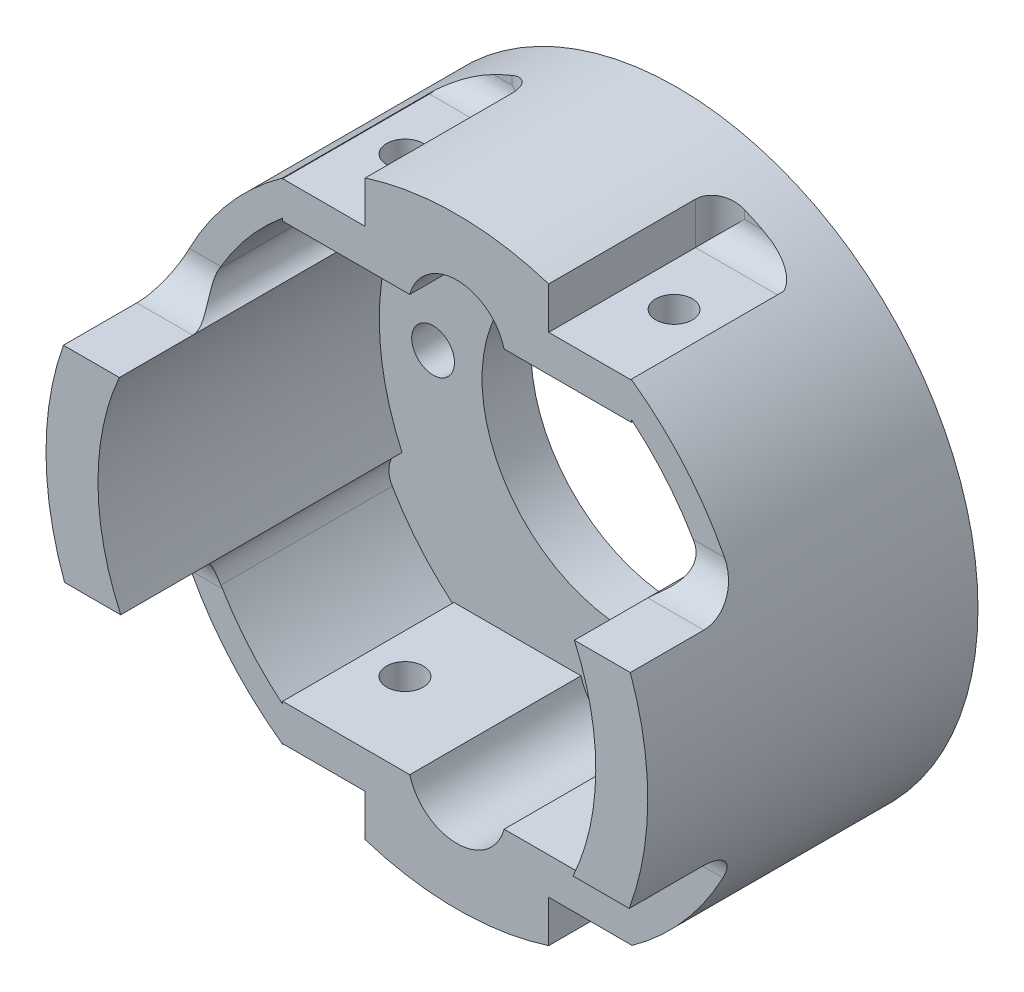
SolidWorks part; units mm, degrees
ref_plane "Front Plane" through (0, 0, 0) normal (0, 0, 1) x (1, 0, 0)
ref_plane "Top Plane" through (0, 0, 0) normal (0, 1, 0) x (1, 0, 0)
ref_plane "Right Plane" through (0, 0, 0) normal (1, 0, 0) x (0, 0, -1)
sketch "Sketch2" plane through (0, 0, 0) normal (0, 0, 1) x (1, 0, 0)
  circle A0 centre (0, 0) radius 11.95 construction
  circle A1 centre (0, 0) radius 24.6 construction
  circle A2 centre (0, 0) radius 11.95
  circle A3 centre (0, 0) radius 24.6
  circle A4 centre (-15.95, 0) radius 1.75
  circle A5 centre (0, 15.95) radius 1.75
  circle A6 centre (15.95, 0) radius 1.75
  circle A7 centre (0, -15.95) radius 1.75
  dimension "D1" = 3.5
extrude "Boss-Extrude1" add sketch "Sketch2" along normal blind 4
sketch "Sketch4" plane through (0, 0, 4) normal (0, 0, 1) x (1, 0, 0)
  line L0 (-12.1464, -17) -> (12.1464, -17) construction
  line L1 (14.25, 20) -> (-14.25, 20)
  line L2 (14.25, 20) -> (14.25, 17)
  line L3 (14.25, 17) -> (-14.25, 17)
  line L4 (-14.25, 20) -> (-14.25, 17)
  line L5 (0, 17) -> (0, 20.0524) construction
  line L6 (14.25, 18.5) -> (-14.25, 18.5) construction
  line L7 (14.25, -17) -> (-14.25, -17)
  line L8 (14.25, -17) -> (14.25, -20)
  line L9 (14.25, -20) -> (-14.25, -20)
  line L10 (-14.25, -17) -> (-14.25, -20)
  line L11 (0, -20) -> (0, -17) construction
  line L12 (14.25, -18.5) -> (-14.25, -18.5) construction
  line L13 (12.1464, 17) -> (-12.1464, 17) construction
  line L14 (14.25, 8.75) -> (14.25, 16.75) construction
  line L15 (-14.25, 16.75) -> (-14.25, 8.75) construction
  line L16 (-14.25, -8.5) -> (-14.25, -16.75) construction
  line L17 (14.25, -16.75) -> (14.25, -8.5) construction
  point P92 (0, 18.5)
  point P107 (0, -18.5)
  dimension "D2" = 3
  dimension "D1" = 3
extrude "Boss-Extrude2" add sketch "Sketch4" along normal blind 14
sketch "Sketch5" plane through (0, -20, 0) normal (0, -1, 0) x (1, 0, 0)
  circle A0 centre (-11, 11.25) radius 1.5
  circle A1 centre (11, 11.25) radius 1.5
  dimension "D2" = 3
  dimension "D1" = 3
extrude "Cut-Extrude1" cut sketch "Sketch5" against normal through all
sketch "Sketch6" plane through (0, 0, 4) normal (0, 0, 1) x (1, 0, 0)
  line L0 (0, 27.4787) -> (0, -26.2951) construction
  line L2 (7.5, 23.4288) -> (7.5, 20)
  line L4 (-7.5, 23.4288) -> (-7.5, 20)
  line L5 (0, -24.6) -> (0, -20) construction
  line L7 (-14.25, -20) -> (14.25, -20) construction
  line L8 (-7.5, -20) -> (7.5, -20)
  line L9 (14.25, 20) -> (-14.25, 20) construction
  line L10 (7.5, 20) -> (-7.5, 20)
  line L11 (-7.5, -20) -> (-7.5, -23.4288)
  line L13 (0, 20) -> (0, 29.517) construction
  line L15 (7.5, -20) -> (7.5, -23.4288)
  circle A0 centre (0, 0) radius 24.6 construction
  arc A1 (-7.5, -23.4288) -> (7.5, -23.4288) centre (0, 0) ccw
  arc A4 (7.5, 23.4288) -> (-7.5, 23.4288) centre (0, 0) ccw
  point P1 (0, 20)
  point P88 (0, -0.8165)
  dimension "D1" = 15
extrude "Boss-Extrude3" add sketch "Sketch6" along normal up to surface (14 mm away) up to face at (0, 18.5, 18)
sketch "Sketch7" plane through (0, 0, 18) normal (0, 0, 1) x (1, 0, 0)
  circle A0 centre (0, -15.95) radius 4
  circle A1 centre (0, 15.95) radius 4
  dimension "D1" = 8
  dimension "D2" = 8
extrude "Cut-Extrude2" cut sketch "Sketch7" against normal up to surface (14 mm away) up to face at (17.7, 0, 4)
fillet "Fillet1" radius 2 8 edges at (7.5, 21.7144, 4) (10.875, 20, 4) (-10.875, 20, 4) (-7.5, 21.7144, 4) (-10.875, -20, 4) (-7.5, -21.7144, 4) (7.5, -21.7144, 4) (10.875, -20, 4)
sketch "Sketch8" plane through (0, 0, 4) normal (0, 0, 1) x (1, 0, 0)
  line L0 (-14.25, -17) -> (-14.25, -20.0524) construction
  line L1 (-14.25, 20.0524) -> (-14.25, 17) construction
  line L2 (-14.25, -17.218) -> (-14.25, -20.0524)
  line L3 (-14.25, 20.0524) -> (-14.25, 17.218)
  line L4 (14.25, 17) -> (14.25, 20.0524) construction
  line L5 (14.25, -20.0524) -> (14.25, -17) construction
  line L6 (14.25, 17.218) -> (14.25, 20.0524)
  line L7 (14.25, -20.0524) -> (14.25, -17.218)
  arc A0 (-14.25, 20.0524) -> (-14.25, -20.0524) centre (0, 0) ccw construction
  arc A1 (-14.25, 20.0524) -> (-14.25, -20.0524) centre (0, 0) ccw
  arc A2 (-14.25, 17.218) -> (-14.25, -17.218) centre (0, 0) ccw
  arc A3 (-12.9466, 18.2183) -> (-12.9466, -18.2183) centre (0, 0) ccw construction
  arc A4 (14.25, -20.0524) -> (14.25, 20.0524) centre (0, 0) ccw construction
  arc A5 (14.25, -20.0524) -> (14.25, 20.0524) centre (0, 0) ccw
  arc A6 (14.25, -17.218) -> (14.25, 17.218) centre (0, 0) ccw
  arc A7 (12.9466, -18.2183) -> (12.9466, 18.2183) centre (0, 0) ccw construction
  dimension "D1" = 2.25
  dimension "D2" = 2.25
extrude "Boss-Extrude4" add sketch "Sketch8" along normal up to surface (14 mm away) up to face at (0, -19.8979, 18)
sketch "Sketch9" plane through (0, 0, 18) normal (0, 0, 1) x (1, 0, 0)
  line L0 (-9.5, -8.5) -> (-14.25, -8.5) construction
  line L1 (23.0848, -8.5) -> (20.6706, -8.5)
  line L3 (23.1754, 8.25) -> (20.7716, 8.25)
  line L5 (12.25, 8.25) -> (-12.25, 8.25) construction
  line L6 (-20.7716, 8.25) -> (-23.1754, 8.25)
  line L7 (-20.6706, -8.5) -> (-23.0848, -8.5)
  line L18 (14.25, 20.0524) -> (14.25, 20)
  line L19 (14.25, 20) -> (7.5, 20)
  line L20 (7.5, 20) -> (7.5, 23.4288)
  line L21 (-7.5, 23.4288) -> (-7.5, 20)
  line L22 (-7.5, 20) -> (-14.25, 20)
  line L23 (-14.25, 20) -> (-14.25, 20.0524)
  line L24 (-14.25, -20.0524) -> (-14.25, -20)
  line L25 (-14.25, -20) -> (-7.5, -20)
  line L26 (-7.5, -20) -> (-7.5, -23.4288)
  line L27 (7.5, -23.4288) -> (7.5, -20)
  line L28 (7.5, -20) -> (14.25, -20)
  line L29 (14.25, -20) -> (14.25, -20.0524)
  arc A0 (14.25, -17.218) -> (14.25, 17.218) centre (0, 0) ccw construction
  arc A1 (20.6706, -8.5) -> (20.7716, 8.25) centre (0, 0) ccw
  arc A2 (-14.25, 17.218) -> (-14.25, -17.218) centre (0, 0) ccw construction
  arc A3 (-20.7716, 8.25) -> (-20.6706, -8.5) centre (0, 0) ccw
  arc A4 (7.5, 23.4288) -> (-7.5, 23.4288) centre (0, 0) ccw
  arc A5 (-14.25, 20.0524) -> (-14.25, -20.0524) centre (0, 0) ccw
  arc A6 (-7.5, -23.4288) -> (7.5, -23.4288) centre (0, 0) ccw
  arc A7 (14.25, -20.0524) -> (14.25, 20.0524) centre (0, 0) ccw
  arc A9 (-23.1754, 8.25) -> (-23.0848, -8.5) centre (0, 0) ccw
  arc A11 (23.0848, -8.5) -> (23.1754, 8.25) centre (0, 0) ccw
  dimension "D1" = 0
extrude "Boss-Extrude5" add sketch "Sketch9" along normal blind 9
fillet "Fillet2" radius 3 4 edges at (-21.9735, 8.25, 18) (-21.8777, -8.5, 18) (21.8777, -8.5, 18) (21.9735, 8.25, 18)
sketch "Sketch10" plane through (0, 0, 27) normal (0, 0, 1) x (1, 0, 0)
  line L0 (-20.7716, 8.25) -> (-18.6027, 8.25)
  line L1 (-20.6706, -8.5) -> (-18.4898, -8.5)
  line L2 (20.7716, 8.25) -> (18.6027, 8.25)
  line L3 (20.6706, -8.5) -> (18.4898, -8.5)
  arc A2 (-18.9129, 7.5117) -> (-18.8209, -7.7394) centre (0, 0) ccw
  arc A3 (-18.6027, 8.25) -> (-18.4898, -8.5) centre (0, 0) ccw
  arc A4 (-20.7716, 8.25) -> (-20.6706, -8.5) centre (0, 0) ccw construction
  arc A5 (18.8209, -7.7394) -> (18.9129, 7.5117) centre (0, 0) ccw
  arc A6 (18.4898, -8.5) -> (18.6027, 8.25) centre (0, 0) ccw
  arc A7 (-20.7716, 8.25) -> (-20.6706, -8.5) centre (0, 0) ccw
  arc A8 (20.6706, -8.5) -> (20.7716, 8.25) centre (0, 0) ccw construction
  arc A9 (20.6706, -8.5) -> (20.7716, 8.25) centre (0, 0) ccw
  point P12 (18.6672, -8.5)
  point P18 (0, 0)
  point P19 (18.4898, 8.25)
  point P21 (-18.6071, 8.25)
  point P23 (-18.6027, -8.5)
  point P25 (-18.6027, -8.5)
  dimension "D1" = 2
  dimension "D2" = 2
extrude "Boss-Extrude6" add sketch "Sketch10" against normal up to surface (23 mm away) up to face at (1.75, -15.95, 4)
fillet "Fillet3" radius 2 4 edges at (20.7716, 8.25, 12.5) (20.6706, -8.5, 12.5) (-20.6706, -8.5, 12.5) (-20.7716, 8.25, 12.5)
equation "\"D2@Sketch4\"=\"D1@Sketch4\""
equation "\"D2@Sketch5\"=\"D1@Sketch5\""
equation "\"D2@Sketch7\"=\"D1@Sketch7\""
